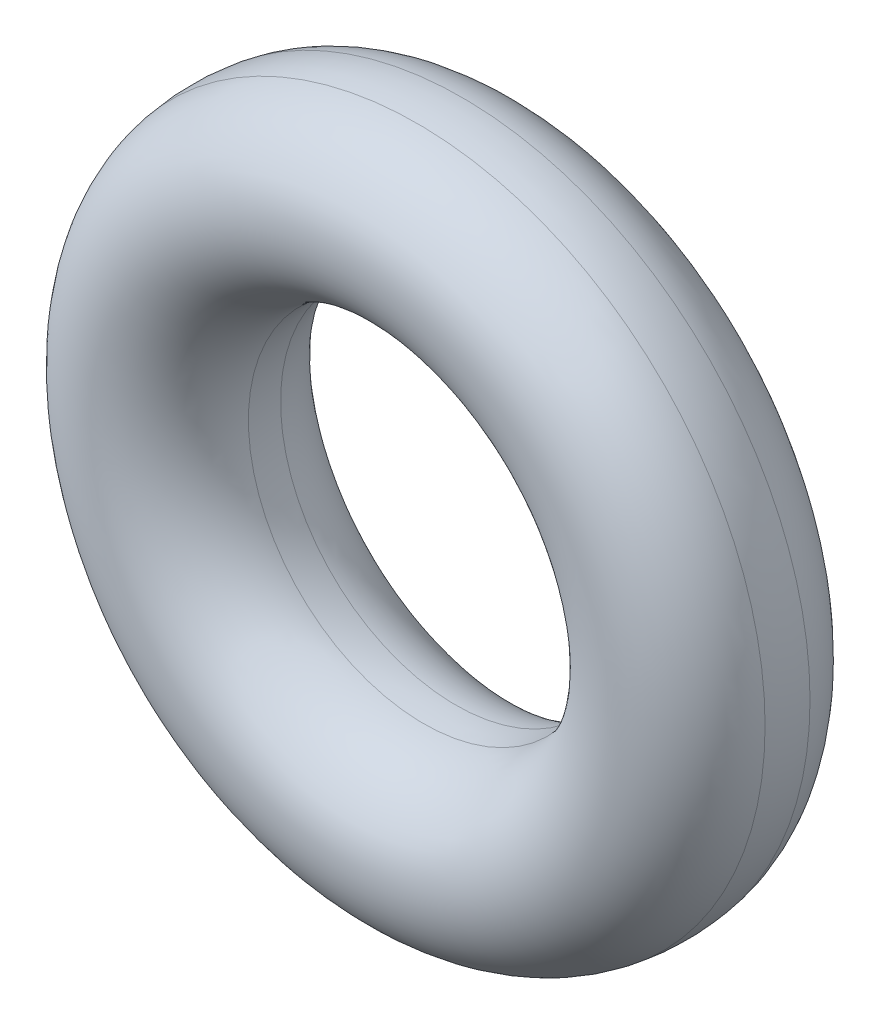
SolidWorks part; units mm, degrees
material "Rubber"
ref_plane "Front Plane" through (0, 0, 0) normal (0, 0, 1) x (1, 0, 0)
ref_plane "Top Plane" through (0, 0, 0) normal (0, 1, 0) x (1, 0, 0)
ref_plane "Right Plane" through (0, 0, 0) normal (1, 0, 0) x (0, 0, -1)
sketch "Sketch4" plane through (0, 0, 0) normal (1, 0, 0) x (0, 0, -1)
  line L0 (-66.289, 0) -> (66.289, 0) construction
  line L1 (0, 0) -> (0, 122.617) construction
  line L2 (-26.7, 73.0769) -> (-26.7, 99.8106) construction
  arc A0 (-6.269, 97.0057) -> (6.269, 97.0057) centre (0, 57.5) cw
  arc A1 (-26.7, 73.0769) -> (-4.4902, 48.933) centre (-2.4718, 73.0769) ccw
  arc A2 (26.7, 73.0769) -> (4.4902, 48.933) centre (2.4718, 73.0769) cw
  arc A3 (-4.4902, 48.933) -> (4.4902, 48.933) centre (0, 102.6452) ccw
  arc A4 (6.269, 97.0057) -> (26.7, 73.0769) centre (2.4718, 73.0769) cw
  arc A5 (-6.269, 97.0057) -> (-26.7, 73.0769) centre (-2.4718, 73.0769) ccw
  arc A6 (-5.7714, 93.8699) -> (5.7714, 93.8699) centre (0, 57.5) cw
  arc A7 (5.7714, 93.8699) -> (23.525, 73.0769) centre (2.4718, 73.0769) cw
  arc A8 (23.525, 73.0769) -> (4.2257, 52.0969) centre (2.4718, 73.0769) cw
  arc A9 (-4.2257, 52.0969) -> (4.2257, 52.0969) centre (0, 102.6452) ccw
  arc A10 (-23.525, 73.0769) -> (-4.2257, 52.0969) centre (-2.4718, 73.0769) ccw
  arc A11 (-5.7714, 93.8699) -> (-23.525, 73.0769) centre (-2.4718, 73.0769) ccw
  dimension "D2" = 40
  dimension "D4" = 24.2282
  dimension "D3" = 53.4
  dimension "D5" = 53.8996
  dimension "D1" = 195
  dimension "D7" = 3.175
revolve "Revolve2" add sketch "Sketch4" angle 360 about L0
ref_axis "Axis1" through (0, 0, 29.37) along (0, 0, -1)
